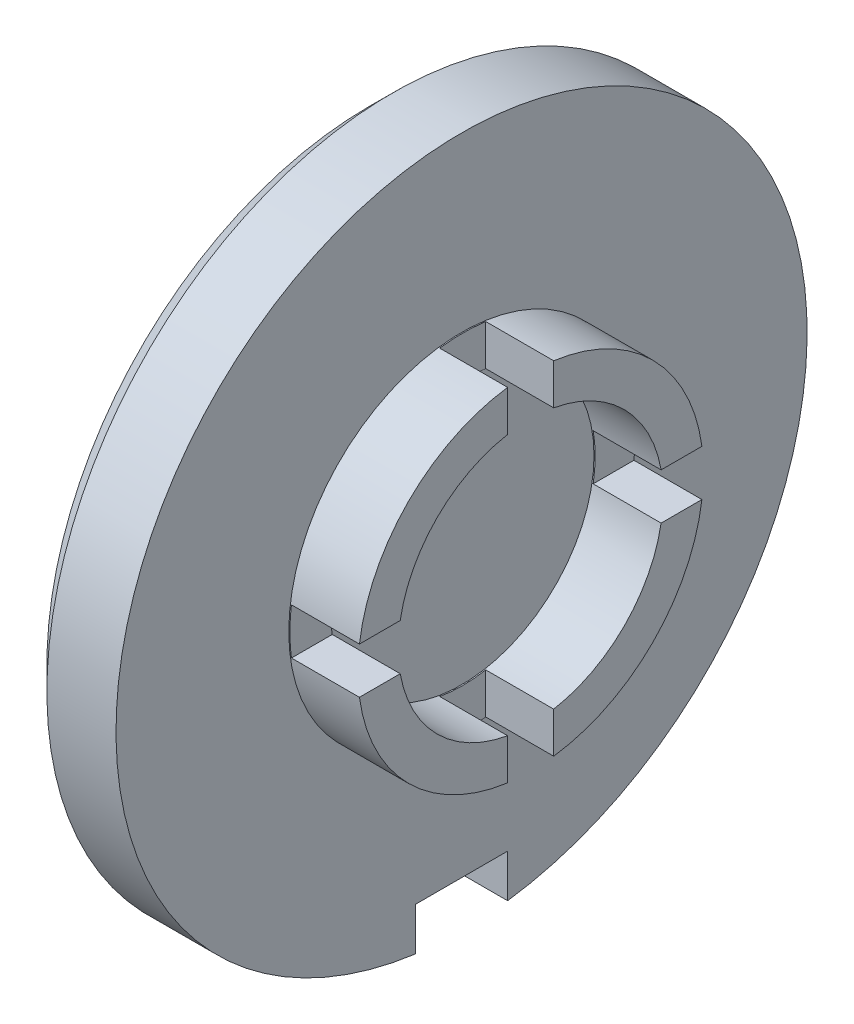
SolidWorks part; units mm, degrees
ref_plane "Front Plane" through (0, 0, 0) normal (0, 0, 1) x (1, 0, 0)
ref_plane "Top Plane" through (0, 0, 0) normal (0, 1, 0) x (1, 0, 0)
ref_plane "Right Plane" through (0, 0, 0) normal (1, 0, 0) x (0, 0, -1)
ref_plane "Plane1" through (0, 0, -52) normal (0, 0, 1) x (1, 0, 0)
sketch "Sketch1" plane through (0, 0, -52) normal (0, 0, 1) x (1, 0, 0)
  line L0 (-81.8, -20) -> (-69, -20) construction
  line L1 (-74, -17.7) -> (-75.2, -17.7)
  line L2 (-75.2, -17.7) -> (-75.2, -20)
  line L3 (-75.2, -20) -> (-76.8, -20)
  line L4 (-76.8, -20) -> (-76.8, -14.4)
  line L5 (-76.8, -14.4) -> (-76.4, -14)
  line L6 (-76.4, -14) -> (-75.2, -14)
  line L7 (-75.2, -14) -> (-75.2, -17)
  line L8 (-75.2, -17) -> (-74, -17)
  line L9 (-74, -17) -> (-74, -17.7)
revolve "Revolve1" add sketch "Sketch1" angle 360 about L0
sketch "Sketch2" plane through (0, 0, 0) normal (0, 0, 1) x (1, 0, 0)
  line L1 (-75.18, -20.4) -> (-73.9, -20.4)
  line L2 (-75.18, -20.4) -> (-75.18, -19.6)
  line L3 (-75.18, -19.6) -> (-73.9, -19.6)
  line L4 (-73.9, -20.4) -> (-73.9, -19.6)
extrude "Boss-Extrude1" add sketch "Sketch2" along normal blind 6.4 from offset 55.2 separate body offset against normal yes
combine bodies "Combine1" operation type subtract main body 101 bodies to subtract 102
sketch "Sketch3" plane through (0, 0, 0) normal (0, 0, 1) x (1, 0, 0)
  line L1 (-75.18, -23.2) -> (-73.9, -23.2)
  line L2 (-75.18, -23.2) -> (-75.18, -16.8)
  line L3 (-75.18, -16.8) -> (-73.9, -16.8)
  line L4 (-73.9, -23.2) -> (-73.9, -16.8)
extrude "Boss-Extrude2" add sketch "Sketch3" along normal blind 0.8 from offset 52.4 separate body offset against normal yes
combine bodies "Combine2" operation type subtract main body 103 bodies to subtract 104
sketch "Sketch4" plane through (0, 0, 0) normal (0, 0, 1) x (1, 0, 0)
  line L1 (-76.9, -26.1) -> (-75.1, -26.1)
  line L2 (-76.9, -26.1) -> (-76.9, -25.2)
  line L3 (-76.9, -25.2) -> (-75.1, -25.2)
  line L4 (-75.1, -26.1) -> (-75.1, -25.2)
extrude "Boss-Extrude3" add sketch "Sketch4" along normal blind 1.6 from offset 52.8 separate body offset against normal yes
combine bodies "Combine3" operation type subtract main body 105 bodies to subtract 106
